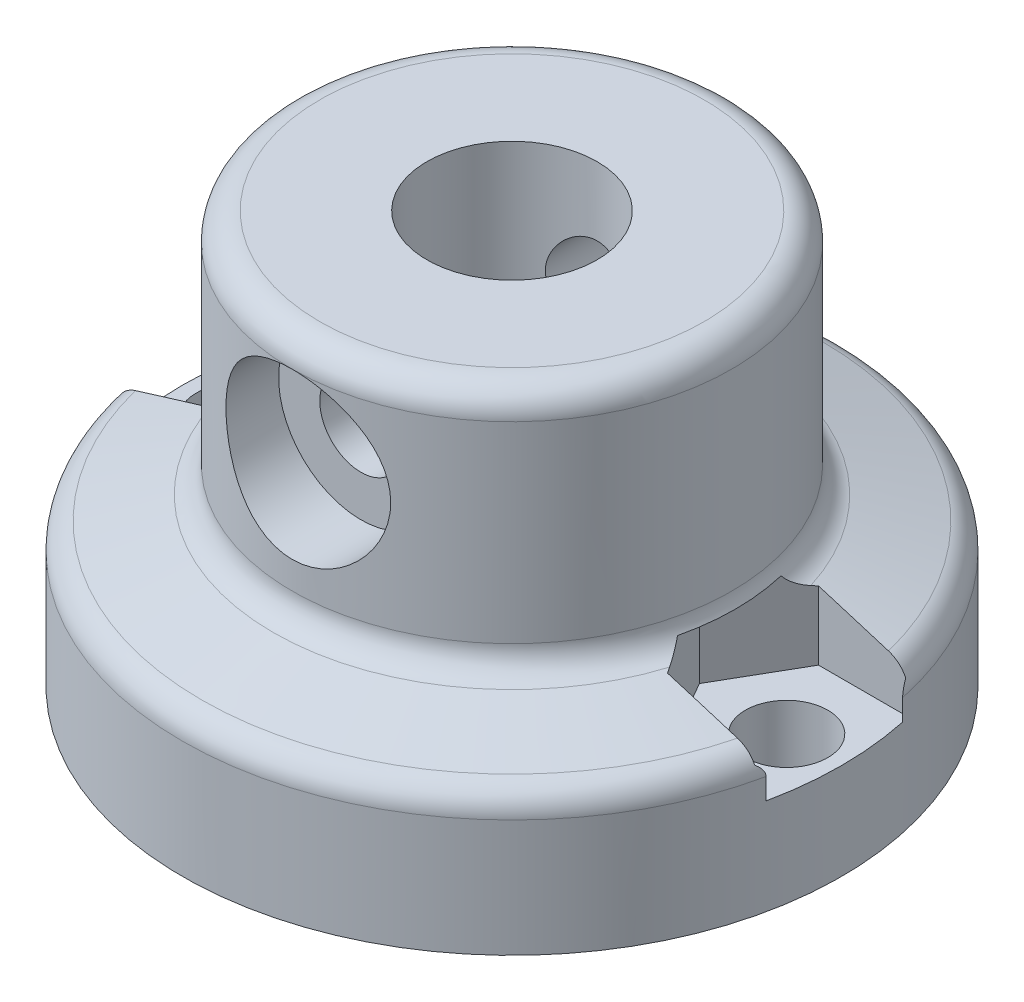
SolidWorks part; units mm, degrees
material "ABS"
ref_plane "Plan de face" through (0, 0, 0) normal (0, 0, 1) x (1, 0, 0)
ref_plane "Plan de dessus" through (0, 0, 0) normal (0, 1, 0) x (1, 0, 0)
ref_plane "Plan de droite" through (0, 0, 0) normal (1, 0, 0) x (0, 0, -1)
sketch "Esquisse1" plane through (0, 0, 0) normal (0, 0, 1) x (1, 0, 0)
  line L0 (0, 0) -> (0, 15) construction
  line L2 (3.1, 15) -> (3.1, 1)
  line L3 (4, 0) -> (12, 0)
  line L4 (12, 0) -> (12, 5)
  line L5 (12, 5) -> (8.6978, 6.0467)
  line L6 (8, 7) -> (8, 15)
  line L7 (8, 15) -> (3.1, 15)
  line L10 (3.1, 1) -> (4, 1)
  line L11 (4, 0) -> (4, 1)
  arc A0 (8.6978, 6.0467) -> (8, 7) centre (9, 7) cw
  dimension "D1" = 6.2
  dimension "D6" = 1
  dimension "D2" = 5
  dimension "D3" = 24
  dimension "D4" = 8
  dimension "D5" = 15
  dimension "D7" = 16
  dimension "D8" = 8
  dimension "D9" = 1
revolve "Révolution1" add sketch "Esquisse1" angle 360 about L0
fillet "Congé1" radius 1 2 edges at (0, 5, -12) (0, 15, -8)
sketch "Esquisse2" plane through (0, 0, 0) normal (0, -1, 0) x (1, 0, 0)
  line L0 (-10, 0) -> (10, 0) construction
  circle A0 centre (-10, 0) radius 1.5
  circle A1 centre (10, 0) radius 1.5
  dimension "D1" = 20
  dimension "D2" = 3
extrude "Enlèv. mat.-Extru.1" cut sketch "Esquisse2" against normal through all
hole_wizard "Chambrage pour vis à tête cylindrique à 6 pans creux (ou vis CHC) M31" positions "Esquisse3D1" profile "Esquisse5" counterbore size "M3" standard "Ansi Metric" end condition through all
sketch3d "Esquisse3D1"
  point P0 (0, 11, 8)
  dimension "D1" = 4
sketch "Esquisse5" plane through (0, 11, 8) normal (1, 0, 0) x (0, -1, 0)
  line L0 (0, 0) -> (0, 20)
  line L1 (0, 20) -> (1.5, 20)
  line L3 (1.5, 20) -> (1.5, 2.5)
  line L4 (1.5, 2.5) -> (3, 2.5)
  line L5 (3, 2.5) -> (3, 0)
  line L7 (3, 0) -> (0, 0)
  line L11 (0, -6.35) -> (0, 107.95) construction
  dimension "Diamètre du perçage jusqu'au prochain" = 3
  dimension "Profondeur du perçage jusqu'au prochain" = 20
  dimension "Diamètre du chambrage" = 6
  dimension "Profondeur du chambrage" = 2.5
sketch "Esquisse3" plane through (0, 0, 0) normal (0, 0, 1) x (1, 0, 0)
  line L2 (2.75, 12.5877) -> (0, 14.1754)
  line L3 (0, 14.1754) -> (-2.75, 12.5877)
  line L4 (-2.75, 12.5877) -> (-2.75, 9.4123)
  line L5 (-2.75, 9.4123) -> (0, 7.8246)
  line L6 (0, 7.8246) -> (2.75, 9.4123)
  line L7 (2.75, 9.4123) -> (2.75, 12.5877)
  circle A0 centre (0, 11) radius 2.75 construction
  dimension "D1" = 5.5
extrude "Enlèv. mat.-Extru.2" cut sketch "Esquisse3" against normal through all from offset 5.5 offset against normal yes
sketch "Esquisse6" plane through (0, 0, 0) normal (0, -1, 0) x (1, 0, 0)
  line L1 (-8.4123, -2.75) -> (-6.8246, 0)
  line L2 (-6.8246, 0) -> (-8.4123, 2.75)
  line L3 (-8.4123, 2.75) -> (-11.5877, 2.75)
  line L4 (-11.5877, 2.75) -> (-13.1754, 0)
  line L5 (-13.1754, 0) -> (-11.5877, -2.75)
  line L6 (-11.5877, -2.75) -> (-8.4123, -2.75)
  line L7 (11.5877, 2.75) -> (8.4123, 2.75)
  line L8 (8.4123, 2.75) -> (6.8246, 0)
  line L9 (6.8246, 0) -> (8.4123, -2.75)
  line L10 (8.4123, -2.75) -> (11.5877, -2.75)
  line L11 (11.5877, -2.75) -> (13.1754, 0)
  line L12 (13.1754, 0) -> (11.5877, 2.75)
  circle A0 centre (-10, 0) radius 2.75 construction
  circle A1 centre (10, 0) radius 2.75 construction
  dimension "D1" = 5.5
extrude "Enlèv. mat.-Extru.3" cut sketch "Esquisse6" against normal blind 3 from offset 3.5 offset against normal yes
chamfer "Chanfrein1" distance 1 angle 45 1 edges at (0, 1, -3.1)
sketch "Esquisse7" plane through (0, 0, 0) normal (0, -1, 0) x (1, 0, 0)
  circle A1 centre (0, 0) radius 12
  circle A2 centre (0, 0) radius 12
  dimension "D1" = 0
extrude "Boss.-Extru.1" [suppressed] add sketch "Esquisse7" against normal blind 0.2
